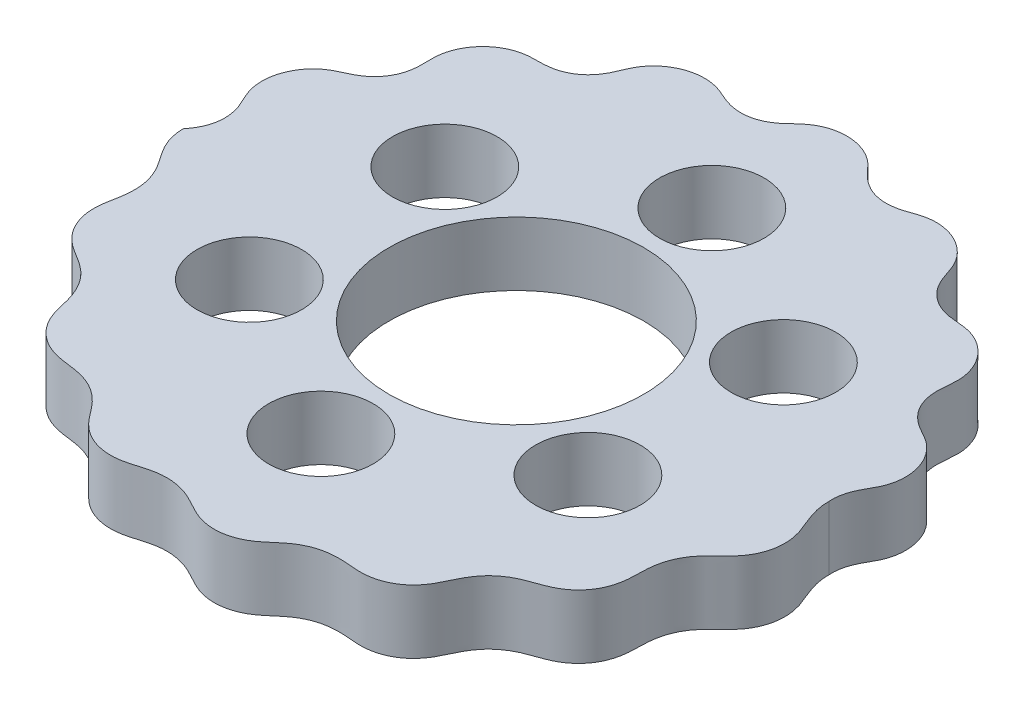
SolidWorks part; units mm, degrees
ref_plane "Front Plane" through (0, 0, 0) normal (0, 0, 1) x (1, 0, 0)
ref_plane "Top Plane" through (0, 0, 0) normal (0, 1, 0) x (1, 0, 0)
ref_plane "Right Plane" through (0, 0, 0) normal (1, 0, 0) x (0, 0, -1)
sketch "Sketch1" plane through (0, 0, 0) normal (0, 1, 0) x (1, 0, 0)
  spline S0 degree 4 poles (34.8883, 9.7527) (35.1064, 9.4428) (35.4821, 8.8015) (35.8088, 7.9292) (35.9688, 6.832) (35.9473, 5.8765) (35.8357, 5.176) (35.6629, 4.5573) (35.4506, 3.9768) (35.2414, 3.4734) (35.011, 2.9332) (34.7849, 2.3453) (34.6177, 1.8074) (34.5045, 1.3247) (34.4413, 0.9462) (34.4087, 0.6762) (34.3917, 0.4776) (34.3834, 0.3371) (34.3777, 0.1912) (34.3746, 0.0487) (34.3746, -0.0478) (34.3777, -0.1898) (34.3833, -0.3348) (34.3914, -0.4744) (34.4082, -0.6718) (34.4404, -0.9399) (34.49, -1.2389) (34.5613, -1.5668) (34.6441, -1.8803) (34.7356, -2.1788) (34.8376, -2.4741) (34.9481, -2.7662) (35.0651, -3.0557) (35.1858, -3.3437) (35.3211, -3.6652) (35.4665, -4.022) (35.6523, -4.5252) (35.8769, -5.3124) (36.0108, -6.3731) (35.8857, -7.6869) (35.4356, -8.9441) (34.7818, -9.9694) (34.0003, -10.8107) (33.1925, -11.5313) (32.3502, -12.3857) (31.5908, -13.4666) (31.0634, -14.7137) (30.8064, -16.0734) (30.7826, -17.3027) (30.7702, -18.386) (30.6088, -19.4924) (30.2505, -20.5876) (29.5865, -21.7108) (28.6344, -22.6684) (27.5779, -23.3326) (26.4967, -23.7612) (25.4661, -24.0919) (24.3721, -24.5481) (23.2801, -25.2325) (22.4312, -26.0549) (21.8123, -26.9219) (21.3901, -27.6879) (21.0939, -28.3072) (20.795, -28.9546) (20.4502, -29.6099) (19.9325, -30.382) (19.1606, -31.1956) (18.0958, -31.9217) (16.8121, -32.3893) (15.542, -32.5414) (14.3664, -32.4646) (13.2896, -32.3545) (12.1193, -32.3527) (10.8784, -32.5548) (9.7832, -32.9781) (8.8621, -33.5428) (8.1548, -34.0958) (7.6134, -34.5663) (7.0676, -35.0374) (6.4863, -35.4714) (5.7055, -35.9313) (4.6889, -36.3248) (3.432, -36.5273) (2.0556, -36.4041) (0.8128, -35.988) (-0.2312, -35.4107) (-1.1765, -34.8828) (-2.2415, -34.4356) (-3.4629, -34.1411) (-4.6469, -34.1107) (-5.7322, -34.284) (-6.6107, -34.5218) (-7.273, -34.7275) (-7.9453, -34.922) (-8.6379, -35.0641) (-9.5274, -35.1465) (-10.6082, -35.0706) (-11.8284, -34.7208) (-13.0361, -34.0168) (-14.0035, -33.0871) (-14.7144, -32.1105) (-15.3775, -31.2537) (-16.1769, -30.4415) (-17.1887, -29.6975) (-18.4309, -29.1417) (-19.6883, -28.8865) (-20.7647, -28.7723) (-21.7754, -28.6194) (-22.7921, -28.3432) (-23.9135, -27.7762) (-25.0057, -26.8226) (-25.7994, -25.6735) (-26.2791, -24.4257) (-26.5218, -23.2538) (-26.7846, -22.2202) (-27.1891, -21.172) (-27.8198, -20.0857) (-28.7391, -19.0818) (-29.9267, -18.2513) (-31.1875, -17.5527) (-32.2814, -16.7162) (-33.1672, -15.6094) (-33.7674, -14.29) (-34.0154, -12.9084) (-33.9331, -11.5606) (-33.6222, -10.1703) (-33.4408, -8.9346) (-33.4817, -7.8127) (-33.686, -6.8058) (-33.9061, -6.1445) (-34.1636, -5.5723) (-34.4548, -5.0401) (-34.7415, -4.5806) (-35.0754, -4.0956) (-35.441, -3.5758) (-35.7471, -3.0985) (-35.9855, -2.6616) (-36.1642, -2.2722) (-36.2945, -1.9377) (-36.4044, -1.5955) (-36.493, -1.2477) (-36.5514, -0.9386) (-36.5877, -0.6711) (-36.6066, -0.474) (-36.6157, -0.3345) (-36.622, -0.1897) (-36.6255, -0.0472) (-36.6255, 0.0498) (-36.6218, 0.1941) (-36.6153, 0.3419) (-36.6058, 0.4839) (-36.5862, 0.6848) (-36.5546, 0.9125) (-36.5136, 1.1383) (-36.4529, 1.4062) (-36.3809, 1.6716) (-36.2808, 1.9763) (-36.1452, 2.317) (-35.9587, 2.7146) (-35.7094, 3.1617) (-35.3897, 3.6508) (-35.0108, 4.1869) (-34.6139, 4.7715) (-34.2299, 5.424) (-33.9059, 6.1306) (-33.6642, 6.8896) (-33.5097, 7.7022) (-33.4639, 8.4365) (-33.4931, 9.1097) (-33.5522, 9.5958) (-33.5887, 9.8378) (-33.6086, 9.9586) knots 0 0 0 0 0 0.010915 0.021327 0.026533 0.03174 0.038371 0.041687 0.045003 0.049536 0.054069 0.058603 0.063136 0.06574 0.068344 0.069645 0.070947 0.071598 0.072249 0.073551 0.074844 0.075491 0.076137 0.077431 0.078724 0.081311 0.083897 0.086145 0.088394 0.090642 0.092891 0.095139 0.097388 0.099636 0.101884 0.105184 0.108484 0.115083 0.125423 0.135762 0.146102 0.153146 0.16019 0.168738 0.177286 0.187634 0.197978 0.207417 0.216856 0.223011 0.229166 0.239505 0.249845 0.260184 0.267673 0.275162 0.283266 0.291369 0.301718 0.312059 0.317001 0.321943 0.326886 0.331828 0.337539 0.343249 0.353588 0.363927 0.374267 0.382199 0.390132 0.397793 0.405454 0.415802 0.426139 0.431304 0.436469 0.441635 0.4468 0.452066 0.457332 0.467671 0.478011 0.488349 0.496727 0.505104 0.512321 0.519539 0.529885 0.541101 0.546095 0.551089 0.556083 0.561077 0.566246 0.571416 0.581754 0.592094 0.602432 0.611256 0.62008 0.626852 0.633624 0.643968 0.656075 0.665617 0.670388 0.675159 0.685498 0.695837 0.706177 0.716515 0.725282 0.734049 0.740626 0.747203 0.757548 0.770045 0.779393 0.788742 0.799079 0.809419 0.819758 0.830097 0.839057 0.848018 0.860789 0.86596 0.871132 0.877574 0.880794 0.884015 0.888592 0.893169 0.897746 0.902323 0.904908 0.907492 0.910077 0.912661 0.915246 0.917831 0.919124 0.920416 0.921062 0.921708 0.923001 0.92432 0.92498 0.92564 0.926959 0.928278 0.930917 0.932236 0.933556 0.936194 0.938832 0.94147 0.944109 0.948836 0.953563 0.95829 0.963017 0.969181 0.975345 0.980623 0.985901 0.992951 0.996475 1 1 1 1 1 construction
  spline S1 degree 4 poles (34.375, 0) (34.375, -0.0381) (34.3756, -0.0954) (34.3777, -0.1898) (34.3833, -0.3348) (34.3914, -0.4744) (34.4082, -0.6718) (34.4404, -0.9399) (34.49, -1.2389) (34.5613, -1.5668) (34.6441, -1.8803) (34.7356, -2.1788) (34.8376, -2.4741) (34.9481, -2.7662) (35.0651, -3.0557) (35.1858, -3.3437) (35.3211, -3.6652) (35.4665, -4.022) (35.6523, -4.5252) (35.8769, -5.3124) (36.0108, -6.3731) (35.8857, -7.6869) (35.4356, -8.9441) (34.7818, -9.9694) (34.0003, -10.8107) (33.1925, -11.5313) (32.3502, -12.3857) (31.5908, -13.4666) (31.0634, -14.7137) (30.8064, -16.0734) (30.7826, -17.3027) (30.7702, -18.386) (30.6088, -19.4924) (30.2505, -20.5876) (29.5865, -21.7108) (28.6344, -22.6684) (27.5779, -23.3326) (26.4967, -23.7612) (25.4661, -24.0919) (24.3721, -24.5481) (23.2801, -25.2325) (22.4312, -26.0549) (21.8123, -26.9219) (21.3901, -27.6879) (21.0939, -28.3072) (20.795, -28.9546) (20.4502, -29.6099) (19.9325, -30.382) (19.1606, -31.1956) (18.0958, -31.9217) (16.8121, -32.3893) (15.542, -32.5414) (14.3664, -32.4646) (13.2896, -32.3545) (12.1193, -32.3527) (10.8784, -32.5548) (9.7832, -32.9781) (8.8621, -33.5428) (8.1548, -34.0958) (7.6134, -34.5663) (7.0676, -35.0374) (6.4863, -35.4714) (5.7055, -35.9313) (4.6889, -36.3248) (3.432, -36.5273) (2.0556, -36.4041) (0.8128, -35.988) (-0.2312, -35.4107) (-1.1765, -34.8828) (-2.2415, -34.4356) (-3.4629, -34.1411) (-4.6469, -34.1107) (-5.7322, -34.284) (-6.6107, -34.5218) (-7.273, -34.7275) (-7.9453, -34.922) (-8.6379, -35.0641) (-9.5274, -35.1465) (-10.6082, -35.0706) (-11.8284, -34.7208) (-13.0361, -34.0168) (-14.0035, -33.0871) (-14.7144, -32.1105) (-15.3775, -31.2537) (-16.1769, -30.4415) (-17.1887, -29.6975) (-18.4309, -29.1417) (-19.6883, -28.8865) (-20.7647, -28.7723) (-21.7754, -28.6194) (-22.7921, -28.3432) (-23.9135, -27.7762) (-25.0057, -26.8226) (-25.7994, -25.6735) (-26.2791, -24.4257) (-26.5218, -23.2538) (-26.7846, -22.2202) (-27.1891, -21.172) (-27.8198, -20.0857) (-28.7391, -19.0818) (-29.9267, -18.2513) (-31.1875, -17.5527) (-32.2814, -16.7162) (-33.1672, -15.6094) (-33.7674, -14.29) (-34.0154, -12.9084) (-33.9331, -11.5606) (-33.6222, -10.1703) (-33.4408, -8.9346) (-33.4817, -7.8127) (-33.686, -6.8058) (-33.9061, -6.1445) (-34.1636, -5.5723) (-34.4548, -5.0401) (-34.7415, -4.5806) (-35.0754, -4.0956) (-35.441, -3.5758) (-35.7471, -3.0985) (-35.9855, -2.6616) (-36.1642, -2.2722) (-36.2945, -1.9377) (-36.4044, -1.5955) (-36.493, -1.2477) (-36.5514, -0.9386) (-36.5877, -0.6711) (-36.6066, -0.474) (-36.6157, -0.3345) (-36.622, -0.1897) (-36.6243, -0.0953) (-36.625, -0.0381) (-36.625, 0) knots 0.073551 0.073551 0.073551 0.073551 0.073551 0.074844 0.075491 0.076137 0.077431 0.078724 0.081311 0.083897 0.086145 0.088394 0.090642 0.092891 0.095139 0.097388 0.099636 0.101884 0.105184 0.108484 0.115083 0.125423 0.135762 0.146102 0.153146 0.16019 0.168738 0.177286 0.187634 0.197978 0.207417 0.216856 0.223011 0.229166 0.239505 0.249845 0.260184 0.267673 0.275162 0.283266 0.291369 0.301718 0.312059 0.317001 0.321943 0.326886 0.331828 0.337539 0.343249 0.353588 0.363927 0.374267 0.382199 0.390132 0.397793 0.405454 0.415802 0.426139 0.431304 0.436469 0.441635 0.4468 0.452066 0.457332 0.467671 0.478011 0.488349 0.496727 0.505104 0.512321 0.519539 0.529885 0.541101 0.546095 0.551089 0.556083 0.561077 0.566246 0.571416 0.581754 0.592094 0.602432 0.611256 0.62008 0.626852 0.633624 0.643968 0.656075 0.665617 0.670388 0.675159 0.685498 0.695837 0.706177 0.716515 0.725282 0.734049 0.740626 0.747203 0.757548 0.770045 0.779393 0.788742 0.799079 0.809419 0.819758 0.830097 0.839057 0.848018 0.860789 0.86596 0.871132 0.877574 0.880794 0.884015 0.888592 0.893169 0.897746 0.902323 0.904908 0.907492 0.910077 0.912661 0.915246 0.917831 0.919124 0.920416 0.921062 0.921708 0.923001 0.923001 0.923001 0.923001 0.923001
  spline S2 degree 4 poles (34.375, 0) (34.3727, 0.0346) (34.3699, 0.0856) (34.366, 0.1785) (34.3639, 0.2867) (34.3639, 0.3704) (34.3659, 0.4743) (34.3712, 0.6017) (34.3817, 0.7512) (34.3996, 0.9205) (34.4234, 1.0895) (34.4603, 1.2993) (34.5345, 1.6324) (34.6716, 2.0814) (34.9132, 2.6545) (35.2648, 3.2938) (35.6497, 3.941) (35.9718, 4.6502) (36.2127, 5.4959) (36.3168, 6.4711) (36.2285, 7.5572) (35.8904, 8.7045) (35.3618, 9.6879) (34.7036, 10.4845) (33.9791, 11.0918) (33.2425, 11.5268) (32.5328, 11.8913) (31.9066, 12.295) (31.253, 12.8344) (30.6231, 13.5559) (30.0845, 14.544) (29.808, 15.6994) (29.7931, 16.6727) (29.867, 17.4284) (29.9228, 17.9758) (29.9491, 18.4156) (29.9431, 18.9664) (29.8531, 19.7128) (29.5866, 20.6301) (29.0506, 21.6477) (28.2589, 22.5913) (27.3676, 23.2855) (26.4515, 23.7455) (25.5599, 24.0067) (24.734, 24.1109) (23.9522, 24.1531) (23.2215, 24.256) (22.5532, 24.4294) (21.9545, 24.6666) (21.2563, 25.0533) (20.5134, 25.6555) (19.9471, 26.3686) (19.5527, 27.1269) (19.3171, 27.7312) (19.1742, 28.1533) (19.0368, 28.5769) (18.8846, 28.9957) (18.6593, 29.5054) (18.2772, 30.1643) (17.6599, 30.9109) (16.7428, 31.6442) (15.6064, 32.2023) (14.4654, 32.4795) (13.4971, 32.5118) (12.7424, 32.4108) (12.0926, 32.2516) (11.4615, 32.0312) (10.6428, 31.7324) (9.5851, 31.5111) (8.3998, 31.5262) (7.3188, 31.8328) (6.4719, 32.2903) (5.7988, 32.8116) (5.2707, 33.3269) (4.7593, 33.9197) (4.1719, 34.5096) (3.42, 35.0554) (2.4959, 35.4991) (1.4016, 35.7799) (0.1709, 35.8294) (-0.9621, 35.6314) (-1.8509, 35.2815) (-2.4965, 34.8963) (-2.9361, 34.5643) (-3.268, 34.2746) (-3.667, 33.8957) (-4.2199, 33.3752) (-4.9991, 32.7919) (-6.0825, 32.3043) (-7.1937, 32.1263) (-8.1497, 32.1836) (-8.9762, 32.371) (-9.6786, 32.6197) (-10.4008, 32.9584) (-11.1955, 33.2754) (-12.1189, 33.4774) (-13.1518, 33.5112) (-14.2673, 33.3258) (-15.4076, 32.8775) (-16.3606, 32.244) (-17.0314, 31.5706) (-17.4671, 30.9623) (-17.7359, 30.4846) (-17.9229, 30.088) (-18.1337, 29.5825) (-18.4227, 28.8844) (-18.887, 28.0345) (-19.6656, 27.1416) (-20.7325, 26.4261) (-21.8542, 26.0447) (-22.8167, 25.9377) (-23.5722, 25.9353) (-24.1199, 25.9322) (-24.5578, 25.9098) (-25.1019, 25.8424) (-25.83, 25.6702) (-26.7076, 25.3053) (-27.6554, 24.6641) (-28.5031, 23.7793) (-29.0979, 22.8176) (-29.4587, 21.8492) (-29.6224, 20.9182) (-29.6308, 20.0627) (-29.5916, 19.2659) (-29.6281, 18.5217) (-29.7684, 17.686) (-30.0783, 16.7797) (-30.6648, 15.8193) (-31.5271, 15.0021) (-32.3626, 14.5026) (-33.0539, 14.1887) (-33.556, 13.9633) (-33.95, 13.7662) (-34.424, 13.4856) (-35.0254, 13.0344) (-35.6865, 12.345) (-36.2998, 11.372) (-36.7212, 10.2146) (-36.8767, 9.0956) (-36.817, 8.0722) (-36.5974, 7.1694) (-36.2746, 6.4021) (-35.9204, 5.704) (-35.6441, 5.0197) (-35.4173, 4.1992) (-35.3323, 3.3992) (-35.3883, 2.5997) (-35.5817, 1.8288) (-35.8119, 1.2418) (-36.1028, 0.7072) (-36.359, 0.3361) (-36.5393, 0.1052) (-36.625, 0) knots 0.07338 0.07338 0.07338 0.07338 0.07338 0.074472 0.075017 0.075563 0.076135 0.076707 0.07785 0.078994 0.080138 0.081281 0.082425 0.084712 0.089287 0.093861 0.099069 0.104277 0.109486 0.114694 0.122573 0.130452 0.138512 0.146571 0.152296 0.158021 0.163745 0.16947 0.173713 0.177956 0.186442 0.195001 0.203561 0.209467 0.212421 0.215374 0.218327 0.22128 0.227187 0.235488 0.24379 0.251894 0.259998 0.265567 0.271137 0.276706 0.282275 0.286582 0.290889 0.295197 0.299504 0.307939 0.316375 0.319362 0.32235 0.325338 0.328326 0.331314 0.334302 0.340277 0.348703 0.357129 0.365555 0.373981 0.379956 0.382944 0.385932 0.391908 0.397883 0.406319 0.414754 0.423368 0.427675 0.431982 0.437552 0.443121 0.44869 0.45426 0.462364 0.470468 0.478769 0.487071 0.492978 0.495931 0.498884 0.501837 0.50479 0.510697 0.519257 0.527816 0.536302 0.540545 0.544788 0.550513 0.556237 0.561962 0.567686 0.575746 0.583806 0.592068 0.60033 0.606208 0.609147 0.612086 0.615025 0.617964 0.623842 0.63236 0.640878 0.649396 0.657914 0.663792 0.666731 0.66967 0.672609 0.675548 0.681426 0.689688 0.69795 0.70601 0.714069 0.719794 0.725519 0.731243 0.736968 0.741211 0.745454 0.75394 0.762499 0.771059 0.776965 0.779919 0.782872 0.785825 0.788778 0.794685 0.802986 0.811288 0.819392 0.827496 0.833065 0.838635 0.844204 0.849773 0.85408 0.858388 0.867002 0.871219 0.875437 0.879655 0.883873 0.887514 0.887514 0.887514 0.887514 0.887514
extrude "Boss-Extrude1" add sketch "Sketch1" along normal blind 7 contours S2 S1
sketch "Sketch2" plane through (0, 7, 0) normal (0, 1, 0) x (1, 0, 0)
  circle A0 centre (0, 0) radius 14
  circle A1 centre (0, 21.5) radius 5.75
  circle A2 centre (18.6195, 10.75) radius 5.75
  circle A3 centre (18.6195, -10.75) radius 5.75
  circle A4 centre (0, -21.5) radius 5.75
  circle A5 centre (-18.6195, -10.75) radius 5.75
  circle A6 centre (-18.6195, 10.75) radius 5.75
  point P17 (4.3301, -2.5)
  point P18 (0, 0)
  point P20 (0, 0)
  dimension "D1" = 28
  dimension "D2" = 11.5
  dimension "D3" = 21.5
  dimension "D4" = 6
extrude "Cut-Extrude1" cut sketch "Sketch2" against normal blind 10
